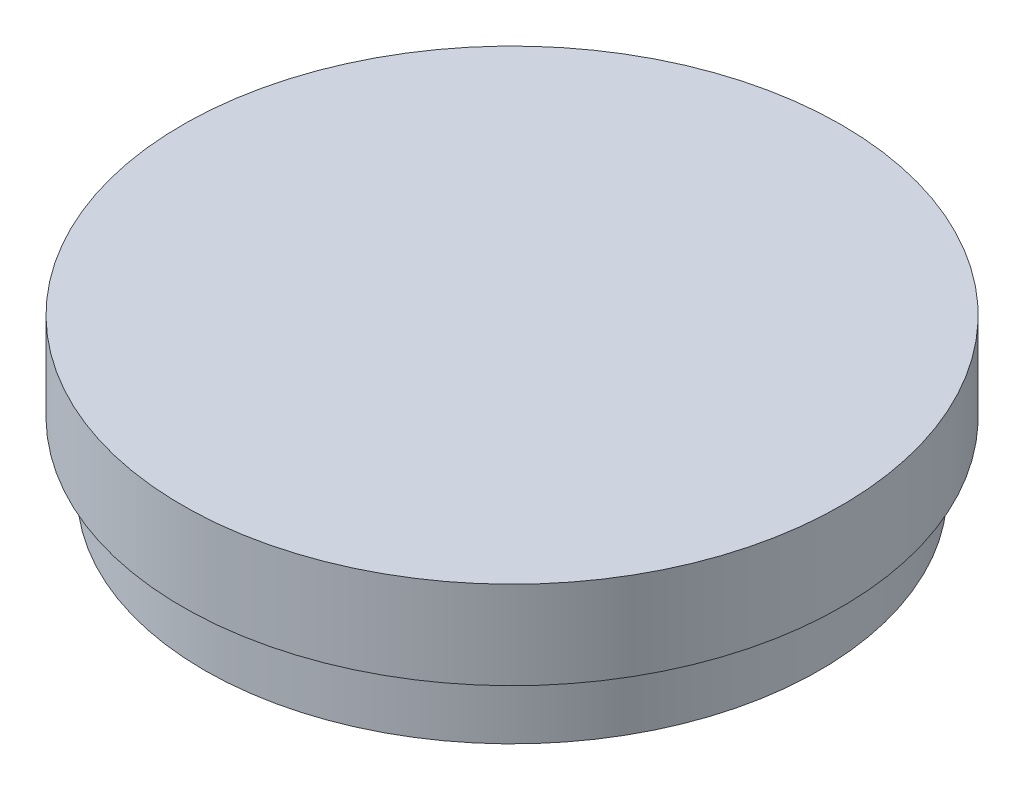
SolidWorks part; units mm, degrees
material "Polyethylene Cross-Linked"
ref_plane "Front Plane" through (0, 0, 0) normal (0, 0, 1) x (1, 0, 0)
ref_plane "Top Plane" through (0, 0, 0) normal (0, 1, 0) x (1, 0, 0)
ref_plane "Right Plane" through (0, 0, 0) normal (1, 0, 0) x (0, 0, -1)
sketch "Sketch1" plane through (0, 0, 0) normal (0, 0, 1) x (1, 0, 0)
  line L0 (0, 0) -> (0, 92.3285) construction
  line L1 (0, 0) -> (88.9, 0)
  line L2 (88.9, 0) -> (88.9, 19.05)
  line L3 (88.9, 19.05) -> (95.25, 19.05)
  line L4 (95.25, 19.05) -> (95.25, 44.45)
  line L5 (95.25, 44.45) -> (0, 44.45)
  line L6 (0, 44.45) -> (0, 0)
  dimension "D1" = 95.25
  dimension "D2" = 6.35
  dimension "D3" = 19.05
  dimension "D4" = 25.4
revolve "Revolve1" add sketch "Sketch1" angle 360 about L0
ref_plane "Plane1" through (0, 0, 101) normal (0, 0, 1) x (1, 0, 0)
ref_plane "Plane2" through (88.9, 0, 0) normal (1, 0, 0) x (0, 0, -1)
sketch "Sketch3" plane through (88.9, 0, 0) normal (1, 0, 0) x (0, 0, -1)
  line L0 (-88.9, 0) -> (88.9, 0) construction
  circle A0 centre (0, 12.7) radius 3.9688
  dimension "D1" = 7.9375
  dimension "D2" = 12.7
extrude "Cut-Extrude1" [suppressed] cut sketch "Sketch3" against normal blind 12.7 contours A0
pattern_circular "CirPattern2" [suppressed] count 4 every 90 of bodies 109
